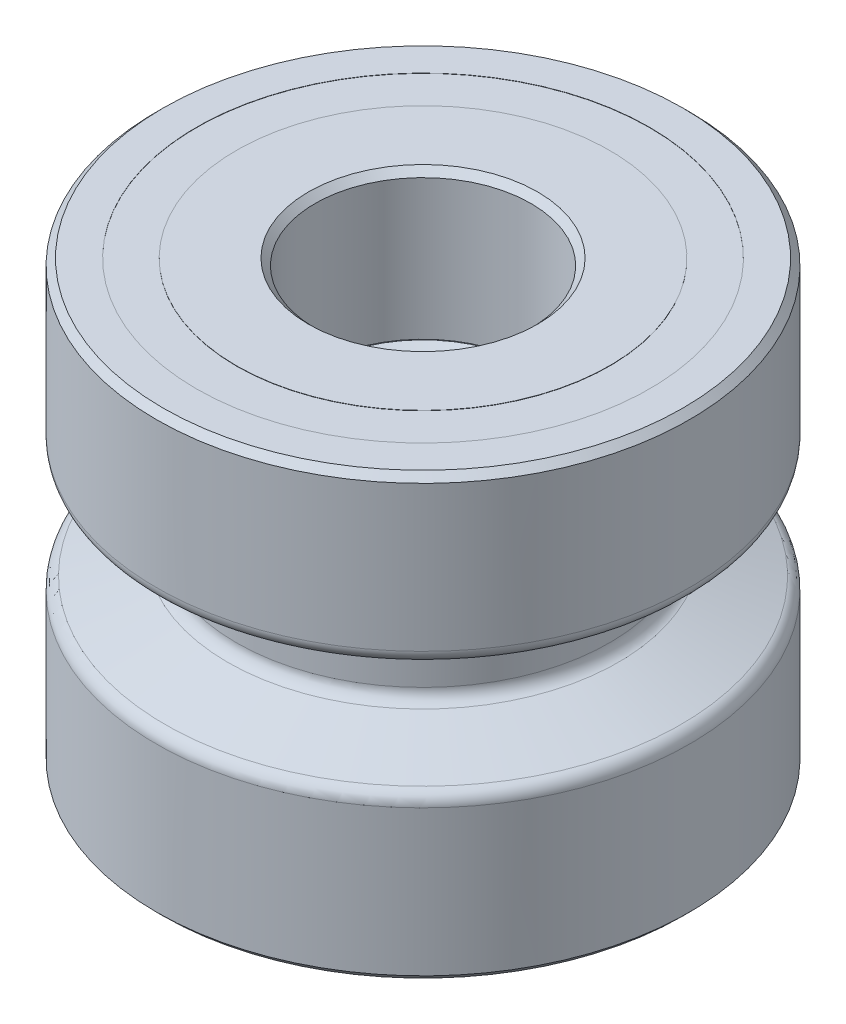
SolidWorks part; units mm, degrees
ref_plane "Front Plane" through (0, 0, 0) normal (0, 0, 1) x (1, 0, 0)
ref_plane "Top Plane" through (0, 0, 0) normal (0, 1, 0) x (1, 0, 0)
ref_plane "Right Plane" through (0, 0, 0) normal (1, 0, 0) x (0, 0, -1)
sketch "Sketch1" plane through (0, 0, 0) normal (0, 1, 0) x (1, 0, 0)
  circle A0 centre (0, 0) radius 10
  dimension "D1" = 20
extrude "Boss-Extrude1" add sketch "Sketch1" along normal mid plane 16.5
sketch "Sketch2" plane through (0, -8.25, 0) normal (0, -1, 0) x (1, 0, 0)
  circle A1 centre (0, 0) radius 3.5
  dimension "D1" = 7
extrude "Cut-Extrude1" cut sketch "Sketch2" against normal up to next
ref_axis "Axis1" through (0, 8.25, 0) along (0, -1, 0)
sketch "Sketch10" plane through (0, 0, 0) normal (0, 0, 1) x (1, 0, 0)
  line L0 (-4.2808, 0) -> (5.2603, 0) construction
  line L1 (10, 2.1919) -> (7, 1.1)
  line L2 (10, -8.25) -> (10, 8.25) construction
  line L4 (10, -2.1919) -> (7, -1.1)
  line L5 (10, 2.1919) -> (10, -2.1919)
  line L6 (7, 1.1) -> (7, -1.1)
  line L7 (7, 1.1) -> (10, 1.1) construction
  dimension "D1" = 3
  dimension "D2" = 2.2
  dimension "D3" = 20
revolve "Cut-Revolve1" cut sketch "Sketch10" angle 360 about axis through (0, 8.25, 0) along (0, -1, 0)
fillet "Fillet4" radius 0.5 4 edges at (0, -1.1, 7) (0, 1.1, 7) (0, 2.1919, 10) (0, -2.1919, 10)
sketch "Sketch11" plane through (0, -8.25, 0) normal (0, -1, 0) x (1, 0, 0)
  circle A0 centre (0, 0) radius 4.05
  dimension "D1" = 8.1
extrude "Cut-Extrude2" cut sketch "Sketch11" against normal blind 2.5
sketch "Sketch12" plane through (0, 8.25, 0) normal (0, 1, 0) x (1, 0, 0)
  circle A0 centre (0, 0) radius 4.05 construction
  circle A1 centre (0, 0) radius 4.05
extrude "Cut-Extrude3" cut sketch "Sketch12" against normal blind 5.5
sketch "Sketch13" plane through (0, 8.25, 0) normal (0, 1, 0) x (1, 0, 0)
  circle A1 centre (0, 0) radius 7
  circle A2 centre (0, 0) radius 8.5
  circle A3 centre (0, 0) radius 8.5
  dimension "D1" = 1.5
  dimension "D2" = 1.5
extrude "Cut-Extrude4" cut sketch "Sketch13" against normal blind 0.01
chamfer "Chamfer1" distance 0.25 angle 45 4 edges at (0, -8.25, 10) (0, -8.25, -4.05) (0, 8.25, 4.05) (0, 8.25, 10)
chamfer "Chamfer2" distance 0.3 angle 60 1 edges at (0, 2.75, 3.5) first distance on face at (0, -5.75, -3.5)
